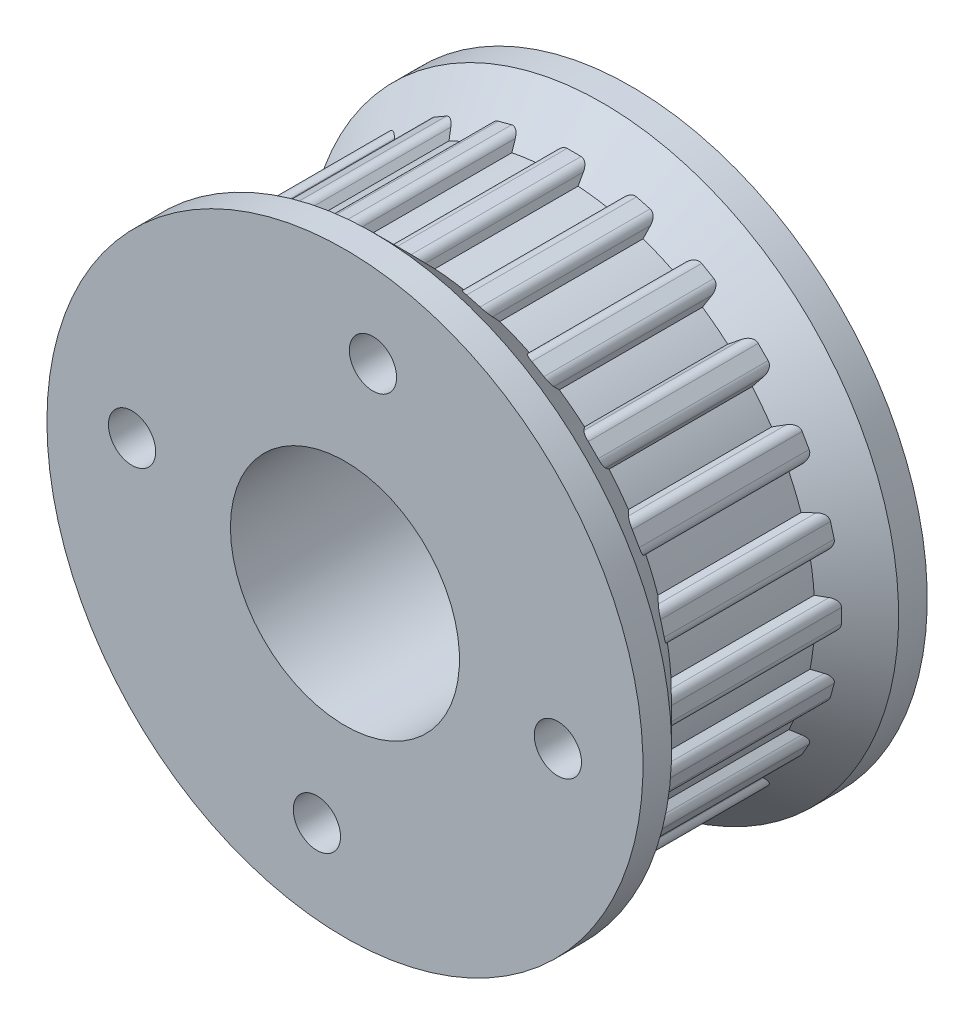
SolidWorks part; units mm, degrees
ref_plane "Plan de face" through (0, 0, 0) normal (0, 0, 1) x (1, 0, 0)
ref_plane "Plan de dessus" through (0, 0, 0) normal (0, 1, 0) x (1, 0, 0)
ref_plane "Plan de droite" through (0, 0, 0) normal (1, 0, 0) x (0, 0, -1)
sketch "Esquisse1" plane through (0, 0, 0) normal (0, 0, 1) x (1, 0, 0)
  line L0 (0, 0) -> (0, 19.1) construction
  line L1 (0, 0) -> (4.9434, 18.4492) construction
  line L2 (0, 0) -> (2.4931, 18.9366) construction
  line L3 (0.4889, 18.6759) -> (0, 18.6759)
  line L4 (1.0685, 18.2312) -> (1.3528, 17.1703)
  line L5 (1.3528, 17.1703) -> (3.1374, 16.9354)
  line L6 (3.6865, 17.8865) -> (3.1374, 16.9354)
  line L7 (4.3614, 18.1661) -> (4.8337, 18.0395)
  line L8 (5.306, 17.913) -> (4.8337, 18.0395)
  line L9 (5.7507, 17.3334) -> (5.7507, 16.2351)
  line L10 (5.7507, 16.2351) -> (7.4136, 15.5463)
  line L11 (8.1902, 16.3229) -> (7.4136, 15.5463)
  line L12 (8.9145, 16.4183) -> (9.3379, 16.1738)
  line L13 (9.7614, 15.9293) -> (9.3379, 16.1738)
  line L14 (10.0409, 15.2544) -> (9.7567, 14.1936)
  line L15 (9.7567, 14.1936) -> (11.1847, 13.0978)
  line L16 (12.1358, 13.6469) -> (11.1847, 13.0978)
  line L17 (12.8601, 13.5516) -> (13.2058, 13.2058)
  line L18 (13.5516, 12.8601) -> (13.2058, 13.2058)
  line L19 (13.6469, 12.1358) -> (13.0978, 11.1847)
  line L20 (13.0978, 11.1847) -> (14.1936, 9.7567)
  line L21 (15.2544, 10.0409) -> (14.1936, 9.7567)
  line L22 (15.9293, 9.7614) -> (16.1738, 9.3379)
  line L23 (16.4183, 8.9145) -> (16.1738, 9.3379)
  line L24 (16.3229, 8.1902) -> (15.5463, 7.4136)
  line L25 (15.5463, 7.4136) -> (16.2351, 5.7507)
  line L26 (17.3334, 5.7507) -> (16.2351, 5.7507)
  line L27 (17.913, 5.306) -> (18.0395, 4.8337)
  line L28 (18.1661, 4.3614) -> (18.0395, 4.8337)
  line L29 (17.8865, 3.6865) -> (16.9354, 3.1374)
  line L30 (16.9354, 3.1374) -> (17.1703, 1.3528)
  line L31 (18.2312, 1.0685) -> (17.1703, 1.3528)
  line L32 (18.6759, 0.4889) -> (18.6759, 0)
  line L33 (18.6759, -0.4889) -> (18.6759, 0)
  line L34 (18.2312, -1.0685) -> (17.1703, -1.3528)
  line L35 (17.1703, -1.3528) -> (16.9354, -3.1374)
  line L36 (17.8865, -3.6865) -> (16.9354, -3.1374)
  line L37 (18.1661, -4.3614) -> (18.0395, -4.8337)
  line L38 (17.913, -5.306) -> (18.0395, -4.8337)
  line L39 (17.3334, -5.7507) -> (16.2351, -5.7507)
  line L40 (16.2351, -5.7507) -> (15.5463, -7.4136)
  line L41 (16.3229, -8.1902) -> (15.5463, -7.4136)
  line L42 (16.4183, -8.9145) -> (16.1738, -9.3379)
  line L43 (15.9293, -9.7614) -> (16.1738, -9.3379)
  line L44 (15.2544, -10.0409) -> (14.1936, -9.7567)
  line L45 (14.1936, -9.7567) -> (13.0978, -11.1847)
  line L46 (13.6469, -12.1358) -> (13.0978, -11.1847)
  line L47 (13.5516, -12.8601) -> (13.2058, -13.2058)
  line L48 (12.8601, -13.5516) -> (13.2058, -13.2058)
  line L49 (12.1358, -13.6469) -> (11.1847, -13.0978)
  line L50 (11.1847, -13.0978) -> (9.7567, -14.1936)
  line L51 (10.0409, -15.2544) -> (9.7567, -14.1936)
  line L52 (9.7614, -15.9293) -> (9.3379, -16.1738)
  line L53 (8.9145, -16.4183) -> (9.3379, -16.1738)
  line L54 (8.1902, -16.3229) -> (7.4136, -15.5463)
  line L55 (7.4136, -15.5463) -> (5.7507, -16.2351)
  line L56 (5.7507, -17.3334) -> (5.7507, -16.2351)
  line L57 (5.306, -17.913) -> (4.8337, -18.0395)
  line L58 (4.3614, -18.1661) -> (4.8337, -18.0395)
  line L59 (3.6865, -17.8865) -> (3.1374, -16.9354)
  line L60 (3.1374, -16.9354) -> (1.3528, -17.1703)
  line L61 (1.0685, -18.2312) -> (1.3528, -17.1703)
  line L62 (0.4889, -18.6759) -> (0, -18.6759)
  line L63 (-0.4889, -18.6759) -> (0, -18.6759)
  line L64 (-1.0685, -18.2312) -> (-1.3528, -17.1703)
  line L65 (-1.3528, -17.1703) -> (-3.1374, -16.9354)
  line L66 (-3.6865, -17.8865) -> (-3.1374, -16.9354)
  line L67 (-4.3614, -18.1661) -> (-4.8337, -18.0395)
  line L68 (-5.306, -17.913) -> (-4.8337, -18.0395)
  line L69 (-5.7507, -17.3334) -> (-5.7507, -16.2351)
  line L70 (-5.7507, -16.2351) -> (-7.4136, -15.5463)
  line L71 (-8.1902, -16.3229) -> (-7.4136, -15.5463)
  line L72 (-8.9145, -16.4183) -> (-9.3379, -16.1738)
  line L73 (-9.7614, -15.9293) -> (-9.3379, -16.1738)
  line L74 (-10.0409, -15.2544) -> (-9.7567, -14.1936)
  line L75 (-9.7567, -14.1936) -> (-11.1847, -13.0978)
  line L76 (-12.1358, -13.6469) -> (-11.1847, -13.0978)
  line L77 (-12.8601, -13.5516) -> (-13.2058, -13.2058)
  line L78 (-13.5516, -12.8601) -> (-13.2058, -13.2058)
  line L79 (-13.6469, -12.1358) -> (-13.0978, -11.1847)
  line L80 (-13.0978, -11.1847) -> (-14.1936, -9.7567)
  line L81 (-15.2544, -10.0409) -> (-14.1936, -9.7567)
  line L82 (-15.9293, -9.7614) -> (-16.1738, -9.3379)
  line L83 (-16.4183, -8.9145) -> (-16.1738, -9.3379)
  line L84 (-16.3229, -8.1902) -> (-15.5463, -7.4136)
  line L85 (-15.5463, -7.4136) -> (-16.2351, -5.7507)
  line L86 (-17.3334, -5.7507) -> (-16.2351, -5.7507)
  line L87 (-17.913, -5.306) -> (-18.0395, -4.8337)
  line L88 (-18.1661, -4.3614) -> (-18.0395, -4.8337)
  line L89 (-17.8865, -3.6865) -> (-16.9354, -3.1374)
  line L90 (-16.9354, -3.1374) -> (-17.1703, -1.3528)
  line L91 (-18.2312, -1.0685) -> (-17.1703, -1.3528)
  line L92 (-18.6759, -0.4889) -> (-18.6759, 0)
  line L93 (-18.6759, 0.4889) -> (-18.6759, 0)
  line L94 (-18.2312, 1.0685) -> (-17.1703, 1.3528)
  line L95 (-17.1703, 1.3528) -> (-16.9354, 3.1374)
  line L96 (-17.8865, 3.6865) -> (-16.9354, 3.1374)
  line L97 (-18.1661, 4.3614) -> (-18.0395, 4.8337)
  line L98 (-17.913, 5.306) -> (-18.0395, 4.8337)
  line L99 (-17.3334, 5.7507) -> (-16.2351, 5.7507)
  line L100 (-16.2351, 5.7507) -> (-15.5463, 7.4136)
  line L101 (-16.3229, 8.1902) -> (-15.5463, 7.4136)
  line L102 (-16.4183, 8.9145) -> (-16.1738, 9.3379)
  line L103 (-15.9293, 9.7614) -> (-16.1738, 9.3379)
  line L104 (-15.2544, 10.0409) -> (-14.1936, 9.7567)
  line L105 (-14.1936, 9.7567) -> (-13.0978, 11.1847)
  line L106 (-13.6469, 12.1358) -> (-13.0978, 11.1847)
  line L107 (-13.5516, 12.8601) -> (-13.2058, 13.2058)
  line L108 (-12.8601, 13.5516) -> (-13.2058, 13.2058)
  line L109 (-12.1358, 13.6469) -> (-11.1847, 13.0978)
  line L110 (-11.1847, 13.0978) -> (-9.7567, 14.1936)
  line L111 (-10.0409, 15.2544) -> (-9.7567, 14.1936)
  line L112 (-9.7614, 15.9293) -> (-9.3379, 16.1738)
  line L113 (-8.9145, 16.4183) -> (-9.3379, 16.1738)
  line L114 (-8.1902, 16.3229) -> (-7.4136, 15.5463)
  line L115 (-7.4136, 15.5463) -> (-5.7507, 16.2351)
  line L116 (-5.7507, 17.3334) -> (-5.7507, 16.2351)
  line L117 (-5.306, 17.913) -> (-4.8337, 18.0395)
  line L118 (-4.3614, 18.1661) -> (-4.8337, 18.0395)
  line L119 (-3.6865, 17.8865) -> (-3.1374, 16.9354)
  line L120 (-3.1374, 16.9354) -> (-1.3528, 17.1703)
  line L121 (-1.0685, 18.2312) -> (-1.3528, 17.1703)
  line L122 (-0.4889, 18.6759) -> (0, 18.6759)
  circle A0 centre (0, 0) radius 19.1 construction
  circle A1 centre (0, 0) radius 18.7 construction
  circle A2 centre (0, 0) radius 17.2 construction
  arc A3 (4.3614, 18.1661) -> (3.6865, 17.8865) centre (4.2061, 17.5865) ccw
  arc A4 (1.0685, 18.2312) -> (0.4889, 18.6759) centre (0.4889, 18.0759) ccw
  arc A5 (8.9145, 16.4183) -> (8.1902, 16.3229) centre (8.6145, 15.8986) ccw
  arc A6 (5.7507, 17.3334) -> (5.306, 17.913) centre (5.1507, 17.3334) ccw
  arc A7 (12.8601, 13.5516) -> (12.1358, 13.6469) centre (12.4358, 13.1273) ccw
  arc A8 (10.0409, 15.2544) -> (9.7614, 15.9293) centre (9.4614, 15.4097) ccw
  arc A9 (15.9293, 9.7614) -> (15.2544, 10.0409) centre (15.4097, 9.4614) ccw
  arc A10 (13.6469, 12.1358) -> (13.5516, 12.8601) centre (13.1273, 12.4358) ccw
  arc A11 (17.913, 5.306) -> (17.3334, 5.7507) centre (17.3334, 5.1507) ccw
  arc A12 (16.3229, 8.1902) -> (16.4183, 8.9145) centre (15.8986, 8.6145) ccw
  arc A13 (18.6759, 0.4889) -> (18.2312, 1.0685) centre (18.0759, 0.4889) ccw
  arc A14 (17.8865, 3.6865) -> (18.1661, 4.3614) centre (17.5865, 4.2061) ccw
  arc A15 (18.1661, -4.3614) -> (17.8865, -3.6865) centre (17.5865, -4.2061) ccw
  arc A16 (18.2312, -1.0685) -> (18.6759, -0.4889) centre (18.0759, -0.4889) ccw
  arc A17 (16.4183, -8.9145) -> (16.3229, -8.1902) centre (15.8986, -8.6145) ccw
  arc A18 (17.3334, -5.7507) -> (17.913, -5.306) centre (17.3334, -5.1507) ccw
  arc A19 (13.5516, -12.8601) -> (13.6469, -12.1358) centre (13.1273, -12.4358) ccw
  arc A20 (15.2544, -10.0409) -> (15.9293, -9.7614) centre (15.4097, -9.4614) ccw
  arc A21 (9.7614, -15.9293) -> (10.0409, -15.2544) centre (9.4614, -15.4097) ccw
  arc A22 (12.1358, -13.6469) -> (12.8601, -13.5516) centre (12.4358, -13.1273) ccw
  arc A23 (5.306, -17.913) -> (5.7507, -17.3334) centre (5.1507, -17.3334) ccw
  arc A24 (8.1902, -16.3229) -> (8.9145, -16.4183) centre (8.6145, -15.8986) ccw
  arc A25 (0.4889, -18.6759) -> (1.0685, -18.2312) centre (0.4889, -18.0759) ccw
  arc A26 (3.6865, -17.8865) -> (4.3614, -18.1661) centre (4.2061, -17.5865) ccw
  arc A27 (-4.3614, -18.1661) -> (-3.6865, -17.8865) centre (-4.2061, -17.5865) ccw
  arc A28 (-1.0685, -18.2312) -> (-0.4889, -18.6759) centre (-0.4889, -18.0759) ccw
  arc A29 (-8.9145, -16.4183) -> (-8.1902, -16.3229) centre (-8.6145, -15.8986) ccw
  arc A30 (-5.7507, -17.3334) -> (-5.306, -17.913) centre (-5.1507, -17.3334) ccw
  arc A31 (-12.8601, -13.5516) -> (-12.1358, -13.6469) centre (-12.4358, -13.1273) ccw
  arc A32 (-10.0409, -15.2544) -> (-9.7614, -15.9293) centre (-9.4614, -15.4097) ccw
  arc A33 (-15.9293, -9.7614) -> (-15.2544, -10.0409) centre (-15.4097, -9.4614) ccw
  arc A34 (-13.6469, -12.1358) -> (-13.5516, -12.8601) centre (-13.1273, -12.4358) ccw
  arc A35 (-17.913, -5.306) -> (-17.3334, -5.7507) centre (-17.3334, -5.1507) ccw
  arc A36 (-16.3229, -8.1902) -> (-16.4183, -8.9145) centre (-15.8986, -8.6145) ccw
  arc A37 (-18.6759, -0.4889) -> (-18.2312, -1.0685) centre (-18.0759, -0.4889) ccw
  arc A38 (-17.8865, -3.6865) -> (-18.1661, -4.3614) centre (-17.5865, -4.2061) ccw
  arc A39 (-18.1661, 4.3614) -> (-17.8865, 3.6865) centre (-17.5865, 4.2061) ccw
  arc A40 (-18.2312, 1.0685) -> (-18.6759, 0.4889) centre (-18.0759, 0.4889) ccw
  arc A41 (-16.4183, 8.9145) -> (-16.3229, 8.1902) centre (-15.8986, 8.6145) ccw
  arc A42 (-17.3334, 5.7507) -> (-17.913, 5.306) centre (-17.3334, 5.1507) ccw
  arc A43 (-13.5516, 12.8601) -> (-13.6469, 12.1358) centre (-13.1273, 12.4358) ccw
  arc A44 (-15.2544, 10.0409) -> (-15.9293, 9.7614) centre (-15.4097, 9.4614) ccw
  arc A45 (-9.7614, 15.9293) -> (-10.0409, 15.2544) centre (-9.4614, 15.4097) ccw
  arc A46 (-12.1358, 13.6469) -> (-12.8601, 13.5516) centre (-12.4358, 13.1273) ccw
  arc A47 (-5.306, 17.913) -> (-5.7507, 17.3334) centre (-5.1507, 17.3334) ccw
  arc A48 (-8.1902, 16.3229) -> (-8.9145, 16.4183) centre (-8.6145, 15.8986) ccw
  arc A49 (-0.4889, 18.6759) -> (-1.0685, 18.2312) centre (-0.4889, 18.0759) ccw
  arc A50 (-3.6865, 17.8865) -> (-4.3614, 18.1661) centre (-4.2061, 17.5865) ccw
  circle A51 centre (0, 0) radius 8
  point P14 (2.2451, 17.0529)
  point P16 (3.9167, 18.2852)
  point P20 (0.9493, 18.6759)
  point P29 (6.5822, 15.8907)
  point P40 (10.4707, 13.6457)
  point P51 (13.6457, 10.4707)
  point P62 (15.8907, 6.5822)
  point P73 (17.0529, 2.2451)
  point P84 (17.0529, -2.2451)
  point P95 (15.8907, -6.5822)
  point P106 (13.6457, -10.4707)
  point P117 (10.4707, -13.6457)
  point P128 (6.5822, -15.8907)
  point P139 (2.2451, -17.0529)
  point P150 (-2.2451, -17.0529)
  point P161 (-6.5822, -15.8907)
  point P172 (-10.4707, -13.6457)
  point P183 (-13.6457, -10.4707)
  point P194 (-15.8907, -6.5822)
  point P205 (-17.0529, -2.2451)
  point P216 (-17.0529, 2.2451)
  point P227 (-15.8907, 6.5822)
  point P238 (-13.6457, 10.4707)
  point P249 (-10.4707, 13.6457)
  point P260 (-6.5822, 15.8907)
  point P271 (-2.2451, 17.0529)
  point P276 (0, 0)
  dimension "D1" = 38.2
  dimension "D2" = 37.4
  dimension "D5" = 1.5
  dimension "D8" = 0.6
  dimension "D10" = 16
  dimension "D3" = 15
  dimension "D4" = 7.5
  dimension "D6" = 15
  dimension "D7" = 1.8
  dimension "D9" = 24
extrude "Boss.-Extru.1" add sketch "Esquisse1" along normal blind 19
sketch "Esquisse3" plane through (0, 0, 0) normal (0, 1, 0) x (1, 0, 0)
  line L0 (-17.7472, -4.5) -> (-17.7472, -14.5)
  line L1 (-17.7472, -14.5) -> (-20.8185, -17.5713)
  line L2 (-20.8185, -17.5713) -> (-20.8185, -19.5713)
  line L3 (-20.8185, -19.5713) -> (-8, -19.5713)
  line L4 (-8, -19.5713) -> (-8, 0.4287)
  line L5 (-8, 0.4287) -> (-20.6759, 0.4287)
  line L6 (-20.6759, 0.4287) -> (-20.6759, -1.5713)
  line L7 (-20.6759, -1.5713) -> (-17.7472, -4.5)
  line L8 (-18.6759, -19) -> (-18.6759, 0) construction
  line L9 (0, 0) -> (0, -19) construction
  line L10 (0.4889, -19) -> (-0.4889, -19) construction
  line L11 (0, -9.5) -> (-17.7472, -9.5) construction
  point P13 (-19.2794, 0.5622)
  point P18 (-20.6759, 5.9978)
  point P19 (-20.8209, -12.5804)
  point P20 (-19.7662, -10)
  point P21 (-4.8388, 5.1459)
  dimension "D1" = 10
  dimension "D2" = 20
  dimension "D3" = 2
  dimension "D4" = 2
  dimension "D5" = 2
  dimension "D6" = 45
  dimension "D7" = 45
  dimension "D8" = 16
revolve "Révolution1" add sketch "Esquisse3" angle 360 about L9
sketch "Esquisse2" plane through (0, 0, -0.4287) normal (0, 0, 1) x (1, 0, 0)
  line L0 (0, 0) -> (1.9579, 14.8717) construction
  line L1 (0, 0) -> (0, 15) construction
  circle A0 centre (0, 0) radius 15 construction
  circle A1 centre (14.8717, -1.9579) radius 1.65
  circle A3 centre (1.9579, 14.8717) radius 1.65
  circle A4 centre (-1.9579, -14.8717) radius 1.65
  circle A5 centre (-14.8717, 1.9579) radius 1.65
  point P3 (0, 0)
  point P5 (0, 15)
  point P15 (0, 0)
  point P19 (0, 0)
  dimension "D1" = 30
  dimension "D2" = 7.5
  dimension "D5" = 3.3
  dimension "D4" = 4
extrude "Enlèv. mat.-Extru.1" cut sketch "Esquisse2" along normal through all
